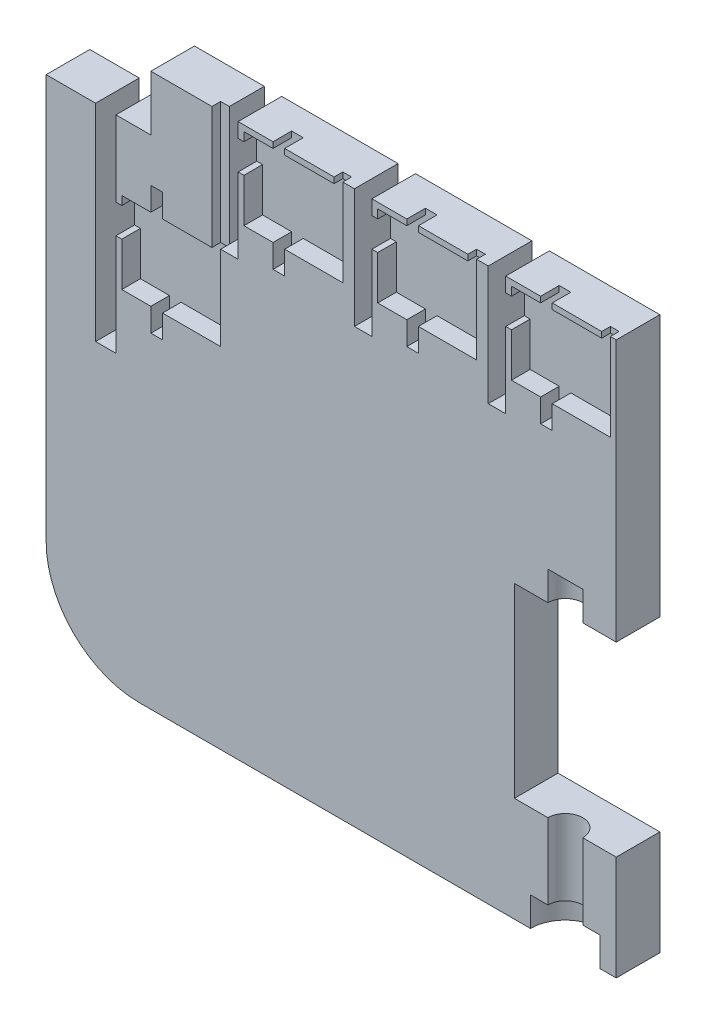
SolidWorks part; units mm, degrees
ref_plane "Front Plane" through (0, 0, 0) normal (0, 0, 1) x (1, 0, 0)
ref_plane "Top Plane" through (0, 0, 0) normal (0, 1, 0) x (1, 0, 0)
ref_plane "Right Plane" through (0, 0, 0) normal (1, 0, 0) x (0, 0, -1)
sketch "Sketch1" plane through (0, 0, 0) normal (0, 0, 1) x (1, 0, 0)
  line L1 (-33, -47.5) -> (49, -47.5)
  line L2 (-49, -31.5) -> (-49, 47.5)
  line L3 (-49, 47.5) -> (27, 47.5)
  line L4 (49, -47.5) -> (49, -29.5)
  line L5 (-49, -47.5) -> (49, 47.5) construction
  line L6 (-49, 47.5) -> (49, -47.5) construction
  line L10 (49, 2.5) -> (31.5, 2.5)
  line L11 (31.5, 2.5) -> (31.5, -29.5)
  line L12 (31.5, -29.5) -> (49, -29.5)
  line L13 (49, 2.5) -> (49, 47.5)
  line L14 (30, 47.5) -> (49, 47.5)
  line L16 (30, 47.5) -> (30, 30.5)
  line L17 (30, 30.5) -> (27, 30.5)
  line L18 (27, 47.5) -> (27, 30.5)
  arc A0 (-33, -47.5) -> (-49, -31.5) centre (-33, -31.5) cw
  point P0 (0, 0)
  point P15 (30, 39)
  dimension "D3" = 16
  dimension "D1" = 98
  dimension "D2" = 95
  dimension "D4" = 18
  dimension "D5" = 17.5
  dimension "D6" = 32
  dimension "D7" = 17
  dimension "D8" = 19
  dimension "D9" = 3
extrude "Boss-Extrude1" add sketch "Sketch1" along normal blind 7.5
sketch "Sketch2" plane through (0, 0, 7.5) normal (0, 0, 1) x (1, 0, 0)
  line L0 (30, 40) -> (31, 40)
  line L1 (30, 47.5) -> (30, 30.5) construction
  line L2 (31, 40) -> (31, 32.5)
  line L3 (31, 32.5) -> (36, 32.5)
  line L4 (36, 32.5) -> (36, 28.5)
  line L5 (36, 28.5) -> (38, 28.5)
  line L6 (38, 28.5) -> (38, 32.5)
  line L7 (38, 32.5) -> (48, 32.5)
  line L8 (48, 32.5) -> (48, 46.5)
  line L9 (48, 46.5) -> (38, 46.5)
  line L10 (31, 46.5) -> (31, 45)
  line L11 (31, 45) -> (30, 45)
  line L12 (30, 45) -> (30, 40)
  line L13 (-16, 40) -> (-15, 40)
  line L14 (36, 46.5) -> (36, 47.5)
  line L15 (49, 47.5) -> (30, 47.5) construction
  line L16 (36, 47.5) -> (38, 47.5)
  line L17 (38, 47.5) -> (38, 46.5)
  line L19 (36, 46.5) -> (31, 46.5)
  line L20 (7, 40) -> (8, 40)
  line L21 (8, 40) -> (8, 32.5)
  line L22 (8, 32.5) -> (13, 32.5)
  line L23 (13, 32.5) -> (13, 28.5)
  line L24 (13, 28.5) -> (15, 28.5)
  line L25 (15, 28.5) -> (15, 32.5)
  line L26 (15, 32.5) -> (25, 32.5)
  line L27 (25, 32.5) -> (25, 46.5)
  line L28 (25, 46.5) -> (15, 46.5)
  line L29 (8, 46.5) -> (8, 45)
  line L30 (8, 45) -> (7, 45)
  line L31 (7, 45) -> (7, 40)
  line L32 (13, 46.5) -> (13, 47.5)
  line L33 (13, 47.5) -> (15, 47.5)
  line L34 (15, 47.5) -> (15, 46.5)
  line L35 (13, 46.5) -> (8, 46.5)
  line L36 (49, 2.5) -> (49, 47.5) construction
  line L37 (27, 47.5) -> (-49, 47.5) construction
  line L38 (-15, 40) -> (-15, 32.5)
  line L39 (-15, 32.5) -> (-10, 32.5)
  line L40 (-10, 32.5) -> (-10, 28.5)
  line L41 (-10, 28.5) -> (-8, 28.5)
  line L42 (-8, 28.5) -> (-8, 32.5)
  line L43 (-8, 32.5) -> (2, 32.5)
  line L44 (2, 32.5) -> (2, 46.5)
  line L45 (2, 46.5) -> (-8, 46.5)
  line L46 (-15, 46.5) -> (-15, 45)
  line L47 (-15, 45) -> (-16, 45)
  line L48 (-16, 45) -> (-16, 40)
  line L49 (-10, 46.5) -> (-10, 47.5)
  line L50 (-10, 47.5) -> (-8, 47.5)
  line L51 (-8, 47.5) -> (-8, 46.5)
  line L52 (-10, 46.5) -> (-15, 46.5)
  point P4 (30, 42.5)
  dimension "D1" = 1
  dimension "D2" = 5
  dimension "D3" = 5
  dimension "D4" = 4
  dimension "D5" = 17
  dimension "D6" = 10
  dimension "D7" = 2
  dimension "D8" = 4
  dimension "D9" = 14
  dimension "D10" = 24
  dimension "D11" = 1
  dimension "D12" = 6
extrude "Cut-Extrude1" cut sketch "Sketch2" against normal blind 3.2
sketch "Sketch3" plane through (0, -47.5, 0) normal (0, -1, 0) x (1, 0, 0)
  line L0 (-33, 7.5) -> (49, 7.5) construction
  line L2 (49, 7.5) -> (31.5, 7.5) construction
  line L4 (34.25, 7.5) -> (46.25, 7.5)
  arc A0 (46.25, 7.5) -> (34.25, 7.5) centre (40.25, 7.5) cw
  point P6 (40.25, 7.5)
  dimension "D2" = 6
  dimension "D1" = 17.5
extrude "Cut-Extrude2" cut sketch "Sketch3" against normal blind 5
sketch "Sketch4" plane through (0, -42.5, 0) normal (0, -1, 0) x (1, 0, 0)
  line L0 (46.25, 7.5) -> (34.25, 7.5) construction
  line L1 (37.25, 7.5) -> (43.25, 7.5)
  arc A0 (43.25, 7.5) -> (37.25, 7.5) centre (40.25, 7.5) cw
  dimension "D1" = 3
extrude "Cut-Extrude3" cut sketch "Sketch4" against normal blind 50
sketch "Sketch5" plane through (0, 0, 7.5) normal (0, 0, 1) x (1, 0, 0)
  line L0 (7, 47.5) -> (7, 30.5)
  line L1 (13, 47.5) -> (-8, 47.5) construction
  line L2 (7, 30.5) -> (4, 30.5)
  line L3 (4, 30.5) -> (4, 47.5)
  line L4 (4, 47.5) -> (7, 47.5)
  line L5 (27, 30.5) -> (27, 47.5) construction
  line L6 (30, 30.5) -> (27, 30.5) construction
  line L7 (7, 45) -> (7, 40) construction
  line L8 (-16, 47.5) -> (-16, 30.5)
  line L9 (-10, 47.5) -> (-49, 47.5) construction
  line L10 (-16, 30.5) -> (-19, 30.5)
  line L11 (-19, 30.5) -> (-19, 47.5)
  line L12 (-19, 47.5) -> (-16, 47.5)
  line L13 (-16, 45) -> (-16, 40) construction
extrude "Cut-Extrude4" cut sketch "Sketch5" against normal up to next
sketch "Sketch8" plane through (0, 0, 7.5) normal (0, 0, 1) x (1, 0, 0)
  line L0 (-19, 47.5) -> (-49, 47.5) construction
  line L1 (-37, 47.5) -> (-49, 47.5)
  line L2 (-37, 47.5) -> (-37, 10.5)
  line L3 (-37, 10.5) -> (-49, 10.5)
  line L4 (-49, 47.5) -> (-49, 10.5)
  line L5 (-49, 47.5) -> (-49, -31.5) construction
  dimension "D1" = 12
  dimension "D2" = 37
extrude "Cut-Extrude5" cut sketch "Sketch8" against normal up to next
sketch "Sketch9" plane through (0, 0, 7.5) normal (0, 0, 1) x (1, 0, 0)
  line L0 (-37, 20) -> (-36, 20)
  line L1 (-36, 20) -> (-36, 12.5)
  line L2 (-36, 12.5) -> (-31, 12.5)
  line L3 (-31, 12.5) -> (-31, 8.5)
  line L4 (-31, 8.5) -> (-29, 8.5)
  line L5 (-29, 8.5) -> (-29, 12.5)
  line L6 (-29, 12.5) -> (-19, 12.5)
  line L7 (-19, 12.5) -> (-19, 26.5)
  line L8 (-19, 26.5) -> (-29, 26.5)
  line L9 (-36, 26.5) -> (-36, 25)
  line L10 (-36, 25) -> (-37, 25)
  line L11 (-37, 25) -> (-37, 20)
  line L12 (-31, 26.5) -> (-31, 30.5)
  line L13 (-31, 30.5) -> (-29, 30.5)
  line L14 (-29, 30.5) -> (-29, 26.5)
  line L15 (-31, 26.5) -> (-36, 26.5)
  line L16 (-49, 10.5) -> (-37, 10.5) construction
  line L17 (-37, 10.5) -> (-37, 47.5) construction
  point P2 (-37, 22.5)
  dimension "D1" = 14
  dimension "D2" = 17
  dimension "D3" = 10
  dimension "D4" = 2
  dimension "D5" = 5
  dimension "D6" = 4
  dimension "D7" = 7.5
  dimension "D8" = 5
  dimension "D9" = 1
  dimension "D10" = 4
  dimension "D11" = 12
extrude "Cut-Extrude6" cut sketch "Sketch9" against normal blind 3.2
sketch "Sketch10" plane through (0, 10.5, 0) normal (0, 1, 0) x (1, 0, 0)
  line L0 (-49, -7.5) -> (-37, -7.5) construction
  line L1 (-49, 0) -> (-39, 0)
  line L2 (-49, 0) -> (-49, -7.5)
  line L3 (-49, -7.5) -> (-39, -7.5)
  line L4 (-39, 0) -> (-39, -7.5)
  dimension "D1" = 10
extrude "Boss-Extrude2" add sketch "Sketch10" along normal blind 27.4864
sketch "Sketch11" plane through (0, 30.5, 0) normal (0, 1, 0) x (1, 0, 0)
  line L1 (-19, 0) -> (-16, 0)
  line L2 (-19, 0) -> (-19, -7.5)
  line L3 (-19, -7.5) -> (-16, -7.5)
  line L4 (-16, 0) -> (-16, -7.5)
  line L5 (4, 0) -> (7, 0)
  line L6 (4, 0) -> (4, -7.5)
  line L7 (4, -7.5) -> (7, -7.5)
  line L8 (7, 0) -> (7, -7.5)
  line L9 (27, 0) -> (30, 0)
  line L10 (27, 0) -> (27, -7.5)
  line L11 (27, -7.5) -> (30, -7.5)
  line L12 (30, 0) -> (30, -7.5)
extrude "Cut-Extrude7" cut sketch "Sketch11" against normal blind 3.5
sketch "Sketch12" plane through (0, 10.5, 0) normal (0, 1, 0) x (1, 0, 0)
  line L1 (-37, 0) -> (-39, 0)
  line L2 (-37, 0) -> (-37, -7.5)
  line L3 (-37, -7.5) -> (-39, -7.5)
  line L4 (-39, 0) -> (-39, -7.5)
extrude "Cut-Extrude8" cut sketch "Sketch12" against normal blind 4
sketch "Sketch13" plane through (0, 6.5, 0) normal (0, 1, 0) x (1, 0, 0)
  line L1 (-39, 0) -> (-37, 0)
  line L2 (-39, 0) -> (-39, -7.5)
  line L3 (-39, -7.5) -> (-37, -7.5)
  line L4 (-37, 0) -> (-37, -7.5)
extrude "Cut-Extrude9" cut sketch "Sketch13" against normal blind 4
sketch "Sketch14" plane through (-37, 0, 0) normal (-1, 0, 0) x (0, 0, 1)
  line L0 (7.5, 25) -> (7.5, 47.5) construction
  line L1 (0, 47.5) -> (7.5, 47.5)
  line L2 (0, 47.5) -> (0, 38)
  line L3 (0, 38) -> (7.5, 38)
  line L4 (7.5, 47.5) -> (7.5, 38)
  dimension "D1" = 13
extrude "Cut-Extrude10" cut sketch "Sketch14" against normal blind 6
sketch "Sketch15" plane through (0, 0, 7.5) normal (0, 0, 1) x (1, 0, 0)
  line L0 (-19, 26.5) -> (-29, 26.5) construction
  line L1 (-19, 47.5) -> (-20.5, 47.5)
  line L2 (-19, 47.5) -> (-19, 26.5)
  line L3 (-19, 26.5) -> (-20.5, 26.5)
  line L4 (-20.5, 47.5) -> (-20.5, 26.5)
  line L5 (4, 47.5) -> (-8, 47.5) construction
  line L6 (2, 46.5) -> (0.5, 46.5)
  line L7 (2, 46.5) -> (2, 47.5)
  line L8 (2, 47.5) -> (0.5, 47.5)
  line L9 (0.5, 46.5) -> (0.5, 47.5)
  line L10 (27, 47.5) -> (15, 47.5) construction
  line L11 (25, 46.5) -> (23.5, 46.5)
  line L12 (25, 46.5) -> (25, 47.5)
  line L13 (25, 47.5) -> (23.5, 47.5)
  line L14 (23.5, 46.5) -> (23.5, 47.5)
  line L15 (49, 47.5) -> (38, 47.5) construction
  line L16 (48, 46.5) -> (46.5, 46.5)
  line L17 (48, 46.5) -> (48, 47.5)
  line L18 (48, 47.5) -> (46.5, 47.5)
  line L19 (46.5, 46.5) -> (46.5, 47.5)
  dimension "D1" = 1.5
  dimension "D2" = 1.5
  dimension "D3" = 1.5
  dimension "D4" = 1.5
extrude "Cut-Extrude11" cut sketch "Sketch15" against normal blind 1.5
ref_plane "Plane1" through (0, 0, 17.5) normal (0, 0, 1) x (1, 0, 0)
sketch "Sketch16" plane through (0, 37.9864, 0) normal (0, 1, 0) x (1, 0, 0)
  line L0 (-39, 0) -> (-49, 0) construction
  line L1 (-40.5, 0) -> (-39, 0)
  line L2 (-40.5, 0) -> (-40.5, -7.5)
  line L3 (-40.5, -7.5) -> (-39, -7.5)
  line L4 (-39, 0) -> (-39, -7.5)
  line L5 (-49, -7.5) -> (-39, -7.5) construction
  line L6 (-49, 0) -> (-49, -7.5) construction
  dimension "D1" = 8.5
  dimension "D2" = 10
extrude "Cut-Extrude12" cut sketch "Sketch16" against normal blind 35.4864
